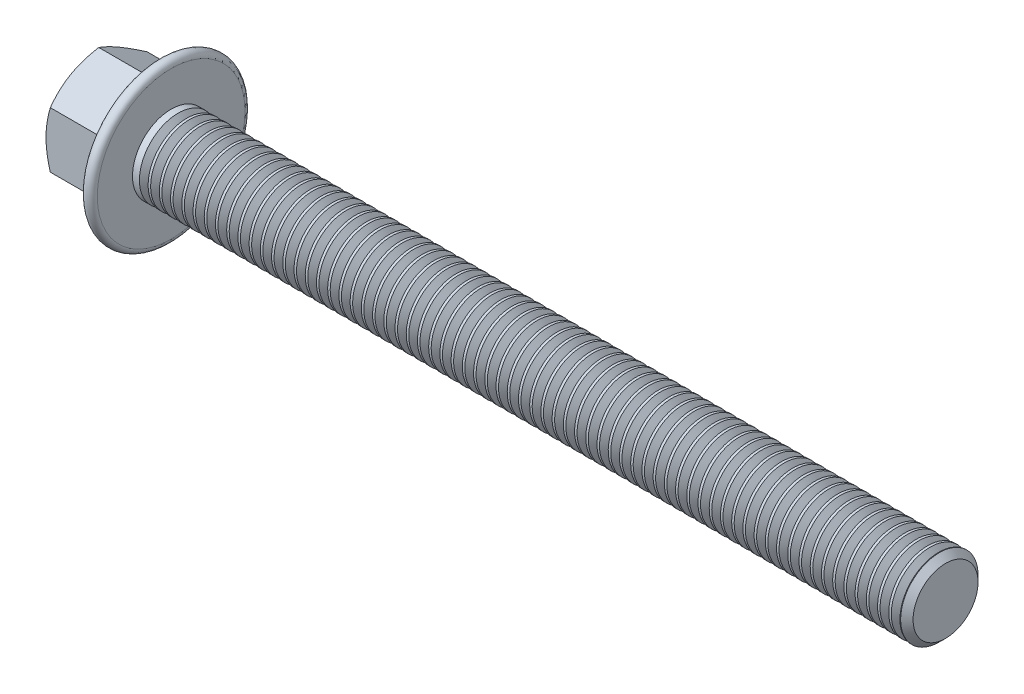
SolidWorks part; units mm, degrees
extrude "BaseHead" add sketch "Sketch1" along normal blind 11.9
sketch "Sketch1" plane through (0, 0, 0) normal (1, 0, 0) x (0, 0, -1)
  line L0 (7.5, 4.3301) -> (7.5, -4.3301)
  line L1 (-7.5, 4.3301) -> (-7.5, -4.3301)
  line L2 (7.5, -4.3301) -> (0, -8.6603)
  line L3 (0, -8.6603) -> (-7.5, -4.3301)
  line L4 (7.5, 4.3301) -> (0, 8.6603)
  line L5 (0, 8.6603) -> (-7.5, 4.3301)
  dimension "D2" = 120
  dimension "D3" = 7.5
  dimension "D4" = 7.5
  dimension "D5" = 7.5
ref_plane "Plane1" through (0, 0, 0) normal (0, 0, 1) x (1, 0, 0)
ref_plane "Plane2" through (0, 0, 0) normal (0, 1, 0) x (1, 0, 0)
ref_plane "Plane3" through (0, 0, 0) normal (1, 0, 0) x (0, 0, -1)
sketch "BodySke" plane through (0, 0, 0) normal (0, 0, 1) x (1, 0, 0)
  line L0 (0, 4.3301) -> (0, -4.3301) construction
  line L1 (0, 0) -> (131.9, 0)
  line L2 (0, 0) -> (0, 6)
  line L3 (0, 6) -> (130.936, 6)
  line L4 (131.9, 0) -> (131.9, 5.036)
  line L5 (11.9, 8.6603) -> (11.9, 4.3301) construction
  line L6 (131.9, 5.036) -> (130.936, 6)
  line L7 (0, 0) -> (96.52, 0) construction
  line L8 (131.9, -5.036) -> (130.936, -6) construction
  line L9 (0, -6) -> (130.936, -6) construction
  line L10 (13.65, 15.24) -> (13.65, -1.27) construction
  line L11 (11.9, 15.24) -> (11.9, -1.27) construction
  line L12 (11.9, 4.3301) -> (11.9, -4.3301) construction
  dimension "Diameter" = 12
revolve "BaseBody" add sketch "BodySke"
cosmetic thread "ThreadCosmetic" [suppressed]
fillet "HeadFillet" [suppressed] radius 0.6
sketch "Sketch3" plane through (0, 0, 0) normal (0, 0, 1) x (1, 0, 0)
  line L0 (0, 7.5) -> (3.5566, 13.6603)
  line L1 (0, 8.6603) -> (0, 4.3301) construction
  line L2 (3.5566, 13.6603) -> (3.5566, 18.6603)
  line L3 (3.5566, 18.6603) -> (-10, 18.6603)
  line L4 (-10, 18.6603) -> (-10, 7.5)
  line L5 (-10, 7.5) -> (0, 7.5)
  line L6 (0, 0) -> (99.06, 0) construction
  line L7 (11.9, 8.6603) -> (0, 8.6603) construction
  dimension "D1" = 7.5
  dimension "D2" = 5
  dimension "D3" = 10
  dimension "D4" = 5
  dimension "Head_ch_ang" = 30
revolve "HeadChamfer" cut sketch "Sketch3" angle 360 about L6
sketch "Sketch4" plane through (0, 0, 0) normal (0, 0, 1) x (1, 0, 0)
  line L0 (5.8748, 0) -> (10.1543, 11.7578)
  line L1 (11.9, 8.6603) -> (11.9, 4.3301) construction
  line L2 (10.1, 34.3444) -> (10.1, 16.9779) construction
  line L3 (11.9, 0) -> (11.9, 11.45)
  line L4 (8.3021, 12.35) -> (20.1618, 12.35) construction
  line L5 (0, 0) -> (95.25, 0) construction
  line L6 (0, 0) -> (96.52, 0) construction
  line L7 (5.8748, 0) -> (11.9, 0)
  line L8 (8.3021, -12.35) -> (20.1618, -12.35) construction
  arc A0 (11.9, 11.45) -> (10.1543, 11.7578) centre (11, 11.45) ccw
  dimension "D1" = 20
  dimension "Flange_thickness" = 1.8
  dimension "Flange_dia" = 24.7
revolve "Flange" add sketch "Sketch4" angle 360 about L5
fillet "FlangeHexFillet" radius 0.24 6 edges
sketch "ThdSchSke" plane through (0, 0, 0) normal (0, 0, 1) x (1, 0, 0)
  line L0 (13.65, -5.036) -> (12.975, -6)
  line L1 (13.65, -5.036) -> (14.325, -6)
  line L2 (14.325, -6) -> (14.325, -7.5)
  line L3 (-3.175, 0) -> (5.1513, 0) construction
  line L5 (14.325, -7.5) -> (12.975, -7.5)
  line L6 (12.975, -7.5) -> (12.975, -6)
  dimension "Thread_minor" = 10.072
  dimension "Diameter" = 12
  dimension "Start" = 13.65
revolve "ThreadSchematic" cut sketch "ThdSchSke" angle 360 about L3
pattern_linear "ThdSchPat" count 68 spacing 1.739 along (1, 0, 0) of "ThreadSchematic"
equation "\"D3@Sketch1\" = \"Width_flats@Sketch1\" / 2"
equation "\"D4@Sketch1\" = \"D3@Sketch1\""
equation "\"D5@Sketch1\" = \"D4@Sketch1\""
equation "\"Thread_minor@ThreadCosmetic\" = \"Minor_dia@BodySke\""
equation "\"D1@Sketch3\" = \"Width_flats@Sketch1\" / 2"
equation "\"Thread_length@ThreadCosmetic\" = ((sgn( (\"Length@BodySke\" - \"Advance@BodySke\" ) - \"Thread_nom@BodySke\" )-1)*( (\"Length@BodySke\" - \"Advance@BodySke\" ) - \"Thread_nom@BodySke\" ))/-2+ \"Thread_nom@BodySke\""
equation "\"Thread_minor@ThdSchSke\" = \"Minor_dia@BodySke\""
equation "\"Diameter@ThdSchSke\" = \"Diameter@BodySke\""
equation "\"Overcut@ThdSchSke\" = \"Diameter@BodySke\" * 1.25"
equation "\"Start@ThdSchSke\" = \"Head_ht@BaseHead\" + \"Length@BodySke\" - \"Thread_length@ThreadCosmetic\"  '---Non-countersunk---"
equation "\"Num_threads@ThdSchPat\" = int( \"Thread_length@ThreadCosmetic\" / \"Advance@BodySke\" + 0.999 )  + 1"
equation "\"Advance@ThdSchPat\" = \"Thread_length@ThreadCosmetic\" /  (\"Num_threads@ThdSchPat\" - 1) 'relax it"
equation "\"Num_threads@ThdSchPat\" = \"Num_threads@ThdSchPat\" - sgn( \"Num_threads@ThdSchPat\" - 1) '---chamfered tips only---"
